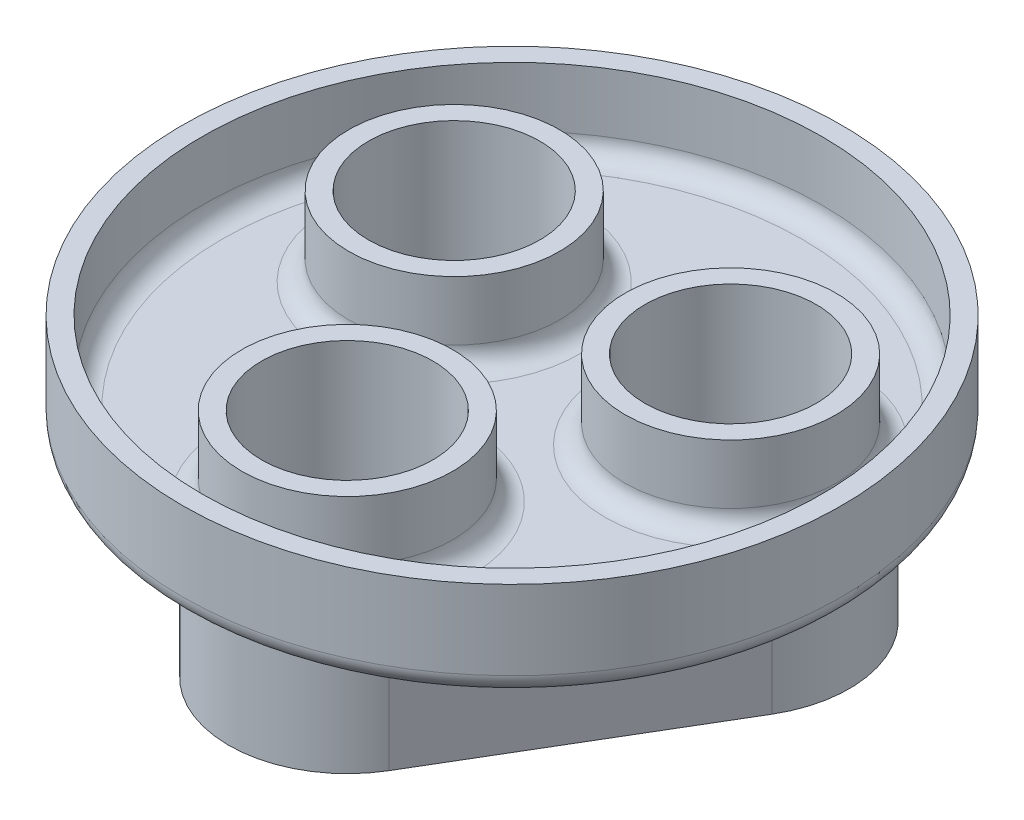
SolidWorks part; units mm, degrees
material "Plain Carbon Steel"
ref_plane "Front Plane" through (0, 0, 0) normal (0, 0, 1) x (1, 0, 0)
ref_plane "Top Plane" through (0, 0, 0) normal (0, 1, 0) x (1, 0, 0)
ref_plane "Right Plane" through (0, 0, 0) normal (1, 0, 0) x (0, 0, -1)
sketch "Sketch1" plane through (0, 0, 0) normal (0, 1, 0) x (1, 0, 0)
  line L0 (0, 0) -> (0, -50) construction
  line L1 (0, 0) -> (-43.3013, 25) construction
  line L2 (0, 0) -> (43.3013, 25) construction
  line L3 (-20.5725, 29.9988) -> (21.8627, 29.4988)
  line L4 (-15.6934, -33.8157) -> (-36.478, 3.1843)
  line L5 (15.4813, -34.183) -> (37.132, 2.317)
  line L6 (-20.2925, -19.5032) -> (-26.6478, -8.1897)
  line L7 (-5.878, 26.8254) -> (7.0975, 26.6725)
  line L9 (20.4164, -19.9828) -> (27.0365, -8.8222)
  line L10 (-13.0778, -32.3464) -> (-33.8625, 4.6536) construction
  line L11 (-20.6079, 26.999) -> (21.8274, 26.499) construction
  line L12 (12.9011, -32.6525) -> (34.5518, 3.8475) construction
  circle A0 centre (0, 0) radius 24 construction
  circle A1 centre (0, 0) radius 50
  circle A2 centre (-20.7846, 12) radius 13
  circle A3 centre (21.6506, 11.5) radius 13
  circle A4 centre (0, -25) radius 13
  arc A6 (-20.5725, 29.9988) -> (-36.478, 3.1843) centre (-20.7846, 12) ccw
  arc A8 (37.132, 2.317) -> (21.8627, 29.4988) centre (21.6506, 11.5) ccw
  arc A9 (-15.6934, -33.8157) -> (15.4813, -34.183) centre (0, -25) ccw
  arc A10 (15.0199, -19.4862) -> (-14.8858, -19.1338) centre (0, -25) ccw
  arc A11 (-23.5195, -3.7645) -> (-8.2614, 21.9584) centre (-20.7846, 12) ccw
  arc A12 (9.3656, 21.7507) -> (24.0133, -4.3246) centre (21.6506, 11.5) ccw
  arc A16 (-14.8858, -19.1338) -> (-20.2925, -19.5032) centre (-17.6769, -18.0339) cw
  arc A17 (-20.6079, 26.999) -> (-33.8625, 4.6536) centre (-20.7846, 12) ccw construction
  circle A18 centre (-20.7846, 12) radius 16 construction
  circle A19 centre (21.6506, 11.5) radius 16 construction
  arc A20 (34.5518, 3.8475) -> (21.8274, 26.499) centre (21.6506, 11.5) ccw construction
  circle A21 centre (0, -25) radius 16 construction
  arc A22 (-13.0778, -32.3464) -> (12.9011, -32.6525) centre (0, -25) ccw construction
  arc A23 (-23.5195, -3.7645) -> (-26.6478, -8.1897) centre (-24.0322, -6.7204) ccw
  arc A24 (15.0199, -19.4862) -> (20.4164, -19.9828) centre (17.8361, -18.4523) ccw
  arc A25 (27.0365, -8.8222) -> (24.0133, -4.3246) centre (24.4563, -7.2917) ccw
  arc A26 (9.3656, 21.7507) -> (7.0975, 26.6725) centre (7.0621, 23.6727) ccw
  arc A27 (-5.878, 26.8254) -> (-8.2614, 21.9584) centre (-5.9133, 23.8256) ccw
  point P15 (0.2887, -0.5)
  point P21 (0.2887, -0.5)
  point P39 (-4.7846, 12)
  point P41 (37.6506, 11.5)
  point P43 (16, -25)
  dimension "D1" = 48
  dimension "D2" = 100
  dimension "D5" = 26
  dimension "D7" = 36
  dimension "D11" = 3
  dimension "D12" = 3
  dimension "D13" = 3
  dimension "D3" = 120
  dimension "D4" = 120
  dimension "D14" = 3
  dimension "D9" = 3
  dimension "D10" = 3
  dimension "D6" = 3
  dimension "D8" = 3
extrude "Boss-Extrude1" add sketch "Sketch1" along normal blind 15 contours A1 A9 L4 A6 L3 A8 L5 | L4 A9 L5 A8 L3 A6 A27 L7 A26 A12 A25 L9 A24 A10 A16 L6 A23 A11 A2 A3 A4 | L7 A27 A11 A23 L6 A16 A10 A24 L9 A25 A12 A26 region at (0.6325, 0, -28.6773) region at (0.2887, 0, 0.5) region at (-48.5858, 0, 0)
extrude "Boss-Extrude3" add sketch "Sketch1<5>" against normal blind 20 contours L4 A9 L5 A8 L3 A6 A27 L7 A26 A12 A25 L9 A24 A10 A16 L6 A23 A11 A2 A3 A4 region at (0.6325, 0, -28.6773)
sketch "Sketch1<5>" plane through (0, 0, 0) normal (0, 1, 0) x (1, 0, 0) same geometry as "Sketch1"
shell "Shell1" thickness 3 removed face at (0, 15, 50)
fillet "Fillet3" radius 3 1 edges at (0, 0, 50)
fillet "Fillet4" radius 3 6 edges at (-0.2121, 0, 42.9988) (26.3067, 0, 15.933) (37.344, 0, -20.3157) (0.6451, 0, -29.7488) (-36.2659, 0, -21.183) (-26.0857, 0, 15.3157)
fillet "Fillet5" radius 3 12 edges at (17.5612, 0, 21.4397) (23.7264, 0, 14.4025) (26.9461, 0, 5.6181) (7.7009, 0, -3.6638) (9.7867, 0, -24.9283) (0.6097, 0, -26.749) (-8.6076, 0, -25.145) (-7.0234, 0, -3.8373) (-26.4819, 0, 4.9886) (-23.4701, 0, 13.8464) (-17.4724, 0, 21.0269) (0.1885, 0, 9.0011)
extrude "Boss-Extrude4" add sketch "Sketch1<7>" along normal up to surface (3 mm away) contours L4 A9 L5 A8 L3 A6 A27 L7 A26 A12 A25 L9 A24 A10 A16 L6 A23 A11 A2 A3 A4 region at (0.6325, 0, -28.6773) up to face at (21.6897, 3, -11.5219)
sketch "Sketch1<7>" plane through (0, 0, 0) normal (0, 1, 0) x (1, 0, 0) same geometry as "Sketch1"
fillet "Fillet6" radius 3 1 edges at (0, 3, 41)
fillet "Fillet7" radius 3 1 edges at (21.6506, 3, 4.5)
fillet "Fillet8" radius 3 1 edges at (-20.7846, 3, 4)
fillet "Fillet9" radius 3 1 edges at (0, 3, 47)
